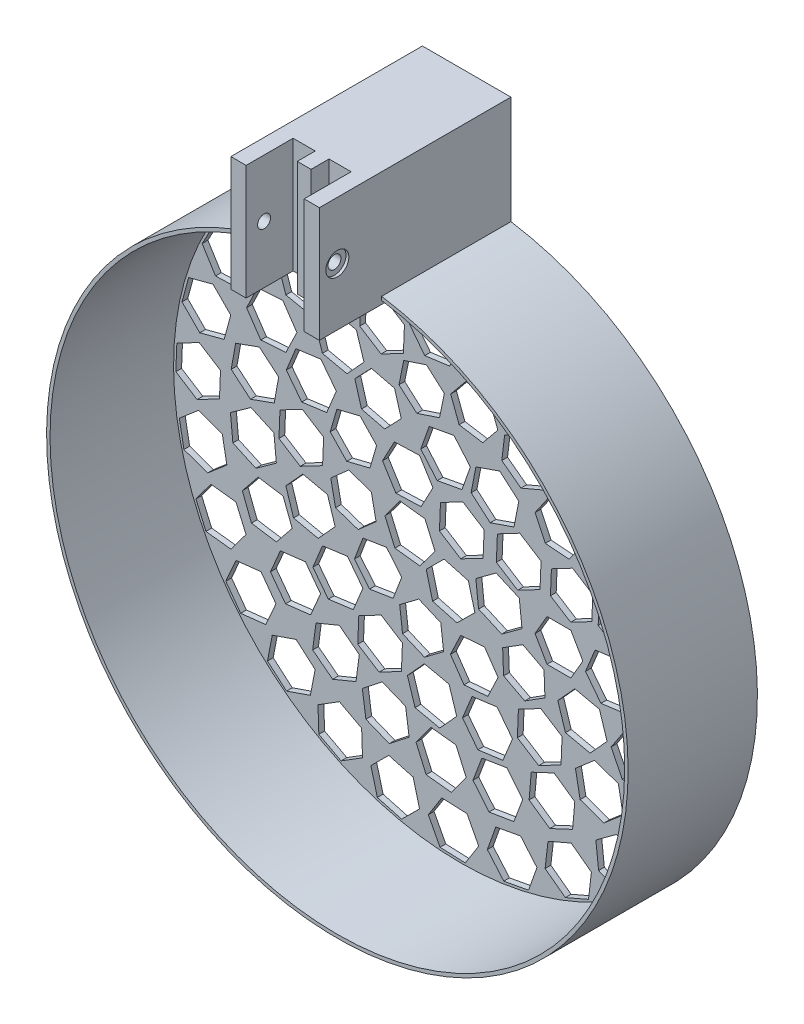
SolidWorks part; units mm, degrees
ref_plane "Plan de face" through (0, 0, 0) normal (0, 0, 1) x (1, 0, 0)
ref_plane "Plan de dessus" through (0, 0, 0) normal (0, 1, 0) x (1, 0, 0)
ref_plane "Plan de droite" through (0, 0, 0) normal (1, 0, 0) x (0, 0, -1)
sketch "Base" plane through (0, 0, 0) normal (0, 1, 0) x (1, 0, 0)
  line L0 (-3.85, -2.4) -> (-3.85, 2.4)
  line L1 (-3.85, 2.4) -> (-10.1, 2.4)
  line L2 (-10.1, 2.4) -> (-10.1, 10.1)
  line L3 (-10.1, 10.1) -> (-2.4, 10.1)
  line L4 (-2.4, 10.1) -> (-2.4, 3.85)
  line L5 (-2.4, 3.85) -> (2.4, 3.85)
  line L6 (0, -55) -> (0, 55) construction
  line L7 (2.4, 10.1) -> (2.4, 3.85)
  line L8 (10.1, 10.1) -> (2.4, 10.1)
  line L9 (10.1, 2.4) -> (10.1, 10.1)
  line L10 (3.85, 2.4) -> (10.1, 2.4)
  line L11 (3.85, -2.4) -> (3.85, 2.4)
  line L12 (-55, 0) -> (55, 0) construction
  line L13 (3.85, -2.4) -> (10.1, -2.4)
  line L14 (10.1, -2.4) -> (10.1, -6.25)
  line L20 (-10.1, -2.4) -> (-10.1, -6.25)
  line L21 (-3.85, -2.4) -> (-10.1, -2.4)
  line L23 (-15.4, 15.4) -> (15.4, 15.4)
  line L24 (-15.4, 15.4) -> (-15.4, -6.25)
  line L26 (15.4, 15.4) -> (15.4, -6.25)
  line L27 (-15.4, 15.4) -> (0, 0) construction
  line L28 (0, 0) -> (15.4, 15.4) construction
  line L29 (-10.1, -6.25) -> (-15.4, -6.25)
  line L30 (10.1, -6.25) -> (15.4, -6.25)
  line L31 (10.1, -10.1) -> (15.4, -15.4) construction
  point P2 (-3.85, 0)
  point P3 (0, 3.85)
  point P27 (0, 0)
  dimension "D1" = 4.8
  dimension "D2" = 4.8
  dimension "D3" = 6.25
  dimension "D4" = 7.7
  dimension "D5" = 30.8
extrude "Boss.-Extru.1" add sketch "Base" along normal mid plane 40
hole_wizard "Chambrage pour vis à six pans creux M41" positions "Esquisse4" profile "Esquisse5" counterbore size "M4" standard "ISO" end condition up to next
sketch "Esquisse4" plane through (15.4, 0, 0) normal (1, 0, 0) x (0, 0, -1)
  point P0 (0, 0)
sketch "Esquisse5" plane through (15.4, 0, 0) normal (0, 1, 0) x (0, 0, -1)
  line L0 (0, 0) -> (0, 11.55)
  line L1 (0, 11.55) -> (2.25, 11.55)
  line L3 (2.25, 11.55) -> (2.25, 1)
  line L4 (2.25, 1) -> (4, 1)
  line L5 (4, 1) -> (4, 0)
  line L7 (4, 0) -> (0, 0)
  line L11 (0, -6.35) -> (0, 107.95) construction
  dimension "Diamètre du perçage jusqu'au prochain" = 4.5
  dimension "Profondeur du perçage jusqu'au prochain" = 11.55
  dimension "Diamètre du chambrage" = 8
  dimension "Profondeur du chambrage" = 1
mirror "Symétrie1" about plane through (0, 0, 0) normal (1, 0, 0) of "Chambrage pour vis à six pans creux M41"
sketch "Esquisse6" plane through (0, 0, 0) normal (0, 0, 1) x (1, 0, 0)
  line L0 (10.1, 20) -> (10.1, -20) construction
  line L1 (-10.1, 20) -> (10.1, 20)
  line L2 (-10.1, 20) -> (-10.1, -20)
  line L3 (-10.1, -20) -> (10.1, -20)
  line L4 (10.1, 20) -> (10.1, -20)
  line L5 (-10.1, 20) -> (10.1, -20) construction
  line L6 (-10.1, -20) -> (10.1, 20) construction
  line L7 (-10.1, 20) -> (-3.85, 20) construction
  point P0 (0, 0)
extrude "Enlèv. mat.-Extru.1" cut sketch "Esquisse6" against normal mid plane 6
sketch "Esquisse16" plane through (0, 0, -15.4) normal (0, 0, -1) x (-1, 0, 0)
  circle A0 centre (0, -117.5665) radius 100
extrude "Extru.-Mince1" add sketch "Esquisse16" along normal blind 45 thin thin type one direction wall 1.2
sketch "Esquisse14" plane through (0, -20, 0) normal (0, -1, 0) x (1, 0, 0)
  line L0 (15.4, 6.25) -> (15.4, -15.4) construction
  line L1 (-15.4, -15.4) -> (15.4, -15.4)
  line L2 (-15.4, -15.4) -> (-15.4, -60.4)
  line L3 (-15.4, -60.4) -> (15.4, -60.4)
  line L4 (15.4, -15.4) -> (15.4, -60.4)
  dimension "D1" = 45
extrude "Boss.-Extru.3" add sketch "Esquisse14" against normal up to vertex (40 mm away) up to point (-15.4, 20, -15.4)
ref_plane "Plan1" through (15.4, -18.7594, -60.4) normal (0.9881, -0.154, 0) x (0, 0, -1)
sketch "Esquisse17" plane through (0, 0, -60.4) normal (0, 0, -1) x (-1, 0, 0)
  circle A0 centre (0, -117.5665) radius 100
extrude "Boss.-Extru.4" add sketch "Esquisse17" against normal blind 2
sketch "Esquisse18" plane through (0, 0, -60.4) normal (0, 0, -1) x (-1, 0, 0)
  line L0 (-29.3876, -106.503) -> (-25.8265, -98.9869)
  line L1 (-31.1629, -121.4274) -> (-31.5026, -113.1172)
  line L2 (-31.5026, -113.1172) -> (-38.8692, -109.2564)
  line L3 (-38.8692, -109.2564) -> (-45.8961, -113.7056)
  line L4 (-45.8961, -113.7056) -> (-45.5564, -122.0158)
  line L5 (-45.5564, -122.0158) -> (-38.1898, -125.8766)
  line L6 (-38.1898, -125.8766) -> (-31.1629, -121.4274)
  line L7 (-25.8265, -98.9869) -> (-30.5551, -92.1448)
  line L8 (-30.5551, -92.1448) -> (-38.8448, -92.8189)
  line L9 (-38.8448, -92.8189) -> (-42.4059, -100.335)
  line L10 (-42.4059, -100.335) -> (-37.6773, -107.177)
  line L11 (-37.6773, -107.177) -> (-29.3876, -106.503)
  line L12 (-20.88, -94.1131) -> (-14.2339, -89.1129)
  line L13 (-14.2339, -89.1129) -> (-15.2412, -80.8571)
  line L14 (-15.2412, -80.8571) -> (-22.8946, -77.6015)
  line L15 (-22.8946, -77.6015) -> (-29.5407, -82.6018)
  line L16 (-29.5407, -82.6018) -> (-28.5334, -90.8576)
  line L17 (-28.5334, -90.8576) -> (-20.88, -94.1131)
  line L18 (-7.589, -87.0962) -> (0.6196, -85.7573)
  line L19 (0.6196, -85.7573) -> (3.5643, -77.979)
  line L20 (3.5643, -77.979) -> (-1.6995, -71.5396)
  line L21 (-1.6995, -71.5396) -> (-9.908, -72.8785)
  line L22 (-9.908, -72.8785) -> (-12.8528, -80.6568)
  line L23 (-12.8528, -80.6568) -> (-7.589, -87.0962)
  line L24 (7.4406, -87.0596) -> (15.3311, -89.6888)
  line L25 (15.3311, -89.6888) -> (21.5533, -84.1699)
  line L26 (21.5533, -84.1699) -> (19.885, -76.0219)
  line L27 (19.885, -76.0219) -> (11.9944, -73.3928)
  line L28 (11.9944, -73.3928) -> (5.7722, -78.9116)
  line L29 (5.7722, -78.9116) -> (7.4406, -87.0596)
  line L30 (20.7656, -94.0118) -> (26.5304, -100.0067)
  line L31 (26.5304, -100.0067) -> (34.6047, -98.0116)
  line L32 (34.6047, -98.0116) -> (36.914, -90.0216)
  line L33 (36.914, -90.0216) -> (31.1491, -84.0267)
  line L34 (31.1491, -84.0267) -> (23.0749, -86.0218)
  line L35 (23.0749, -86.0218) -> (20.7656, -94.0118)
  line L36 (29.3334, -106.3601) -> (31.652, -114.3474)
  line L37 (31.652, -114.3474) -> (39.7285, -116.3331)
  line L38 (39.7285, -116.3331) -> (45.4864, -110.3315)
  line L39 (45.4864, -110.3315) -> (43.1679, -102.3442)
  line L40 (43.1679, -102.3442) -> (35.0913, -100.3585)
  line L41 (35.0913, -100.3585) -> (29.3334, -106.3601)
  line L42 (31.1813, -121.2756) -> (29.5224, -129.4255)
  line L43 (29.5224, -129.4255) -> (35.751, -134.9371)
  line L44 (35.751, -134.9371) -> (43.6385, -132.2988)
  line L45 (43.6385, -132.2988) -> (45.2974, -124.1489)
  line L46 (45.2974, -124.1489) -> (39.0688, -118.6373)
  line L47 (39.0688, -118.6373) -> (31.1813, -121.2756)
  line L48 (25.886, -135.3414) -> (20.6296, -141.7869)
  line L49 (20.6296, -141.7869) -> (23.5834, -149.5618)
  line L50 (23.5834, -149.5618) -> (31.7935, -150.8912)
  line L51 (31.7935, -150.8912) -> (37.0499, -144.4457)
  line L52 (37.0499, -144.4457) -> (34.0961, -136.6708)
  line L53 (34.0961, -136.6708) -> (25.886, -135.3414)
  line L54 (14.6605, -145.3352) -> (7.0109, -148.5997)
  line L55 (7.0109, -148.5997) -> (6.0131, -156.8567)
  line L56 (6.0131, -156.8567) -> (12.665, -161.8492)
  line L57 (12.665, -161.8492) -> (20.3147, -158.5848)
  line L58 (20.3147, -158.5848) -> (21.3124, -150.3278)
  line L59 (21.3124, -150.3278) -> (14.6605, -145.3352)
  line L60 (0.0764, -148.9676) -> (-8.214, -148.3031)
  line L61 (-8.214, -148.3031) -> (-12.9347, -155.1507)
  line L62 (-12.9347, -155.1507) -> (-9.3649, -162.6626)
  line L63 (-9.3649, -162.6626) -> (-1.0744, -163.3271)
  line L64 (-1.0744, -163.3271) -> (3.6462, -156.4795)
  line L65 (3.6462, -156.4795) -> (0.0764, -148.9676)
  line L66 (-14.5251, -145.4063) -> (-21.5572, -140.9652)
  line L67 (-21.5572, -140.9652) -> (-28.9193, -144.8346)
  line L68 (-28.9193, -144.8346) -> (-29.2494, -153.1451)
  line L69 (-29.2494, -153.1451) -> (-22.2173, -157.5862)
  line L70 (-22.2173, -157.5862) -> (-14.8552, -153.7168)
  line L71 (-14.8552, -153.7168) -> (-14.5251, -145.4063)
  line L72 (-25.7992, -135.4672) -> (-29.9619, -128.2669)
  line L73 (-29.9619, -128.2669) -> (-38.2789, -128.2717)
  line L74 (-38.2789, -128.2717) -> (-42.4332, -135.4769)
  line L75 (-42.4332, -135.4769) -> (-38.2705, -142.6772)
  line L76 (-38.2705, -142.6772) -> (-29.9535, -142.6724)
  line L77 (-29.9535, -142.6724) -> (-25.7992, -135.4672)
  line L78 (-47.7791, -122.0417) -> (-48.1377, -113.2706)
  line L79 (-48.1377, -113.2706) -> (-55.913, -109.1955)
  line L80 (-55.913, -109.1955) -> (-63.3297, -113.8916)
  line L81 (-63.3297, -113.8916) -> (-62.9711, -122.6627)
  line L82 (-62.9711, -122.6627) -> (-55.1958, -126.7378)
  line L83 (-55.1958, -126.7378) -> (-47.7791, -122.0417)
  line L84 (-46.4283, -105.4304) -> (-43.7653, -97.0656)
  line L85 (-43.7653, -97.0656) -> (-49.6779, -90.577)
  line L86 (-49.6779, -90.577) -> (-58.2536, -92.4532)
  line L87 (-58.2536, -92.4532) -> (-60.9165, -100.818)
  line L88 (-60.9165, -100.818) -> (-55.0039, -107.3066)
  line L89 (-55.0039, -107.3066) -> (-46.4283, -105.4304)
  line L90 (-39.4775, -90.2829) -> (-34.1142, -83.3333)
  line L91 (-34.1142, -83.3333) -> (-37.451, -75.2138)
  line L92 (-37.451, -75.2138) -> (-46.1512, -74.0438)
  line L93 (-46.1512, -74.0438) -> (-51.5145, -80.9934)
  line L94 (-51.5145, -80.9934) -> (-48.1777, -89.1129)
  line L95 (-48.1777, -89.1129) -> (-39.4775, -90.2829)
  line L96 (-27.7652, -78.4262) -> (-20.3484, -73.7301)
  line L97 (-20.3484, -73.7301) -> (-20.707, -64.959)
  line L98 (-20.707, -64.959) -> (-28.4823, -60.8839)
  line L99 (-28.4823, -60.8839) -> (-35.899, -65.58)
  line L100 (-35.899, -65.58) -> (-35.5405, -74.3511)
  line L101 (-35.5405, -74.3511) -> (-27.7652, -78.4262)
  line L102 (-12.704, -71.2904) -> (-4.1283, -69.4142)
  line L103 (-4.1283, -69.4142) -> (-1.4654, -61.0494)
  line L104 (-1.4654, -61.0494) -> (-7.378, -54.5608)
  line L105 (-7.378, -54.5608) -> (-15.9536, -56.437)
  line L106 (-15.9536, -56.437) -> (-18.6166, -64.8018)
  line L107 (-18.6166, -64.8018) -> (-12.704, -71.2904)
  line L108 (3.8895, -69.7362) -> (12.5897, -70.9061)
  line L109 (12.5897, -70.9061) -> (17.953, -63.9566)
  line L110 (17.953, -63.9566) -> (14.6162, -55.8371)
  line L111 (14.6162, -55.8371) -> (5.916, -54.6671)
  line L112 (5.916, -54.6671) -> (0.5527, -61.6166)
  line L113 (0.5527, -61.6166) -> (3.8895, -69.7362)
  line L114 (20.0139, -73.951) -> (27.7892, -78.026)
  line L115 (27.7892, -78.026) -> (35.206, -73.3299)
  line L116 (35.206, -73.3299) -> (34.8474, -64.5588)
  line L117 (34.8474, -64.5588) -> (27.0721, -60.4838)
  line L118 (27.0721, -60.4838) -> (19.6554, -65.1799)
  line L119 (19.6554, -65.1799) -> (20.0139, -73.951)
  line L120 (33.7243, -83.4265) -> (39.637, -89.9151)
  line L121 (39.637, -89.9151) -> (48.2126, -88.0389)
  line L122 (48.2126, -88.0389) -> (50.8755, -79.6741)
  line L123 (50.8755, -79.6741) -> (44.9629, -73.1855)
  line L124 (44.9629, -73.1855) -> (36.3873, -75.0617)
  line L125 (36.3873, -75.0617) -> (33.7243, -83.4265)
  line L126 (43.3671, -97.0198) -> (46.7039, -105.1393)
  line L127 (46.7039, -105.1393) -> (55.404, -106.3093)
  line L128 (55.404, -106.3093) -> (60.7673, -99.3597)
  line L129 (60.7673, -99.3597) -> (57.4305, -91.2402)
  line L130 (57.4305, -91.2402) -> (48.7304, -90.0702)
  line L131 (48.7304, -90.0702) -> (43.3671, -97.0198)
  line L132 (47.7791, -113.0913) -> (48.1377, -121.8624)
  line L133 (48.1377, -121.8624) -> (55.913, -125.9375)
  line L134 (55.913, -125.9375) -> (63.3297, -121.2414)
  line L135 (63.3297, -121.2414) -> (62.9711, -112.4703)
  line L136 (62.9711, -112.4703) -> (55.1958, -108.3952)
  line L137 (55.1958, -108.3952) -> (47.7791, -113.0913)
  line L138 (46.4283, -129.7026) -> (43.7653, -138.0674)
  line L139 (43.7653, -138.0674) -> (49.6779, -144.556)
  line L140 (49.6779, -144.556) -> (58.2536, -142.6798)
  line L141 (58.2536, -142.6798) -> (60.9165, -134.315)
  line L142 (60.9165, -134.315) -> (55.0039, -127.8264)
  line L143 (55.0039, -127.8264) -> (46.4283, -129.7026)
  line L144 (39.4775, -144.8501) -> (34.1142, -151.7997)
  line L145 (34.1142, -151.7997) -> (37.451, -159.9192)
  line L146 (37.451, -159.9192) -> (46.1512, -161.0892)
  line L147 (46.1512, -161.0892) -> (51.5145, -154.1396)
  line L148 (51.5145, -154.1396) -> (48.1777, -146.0201)
  line L149 (48.1777, -146.0201) -> (39.4775, -144.8501)
  line L150 (27.7652, -156.7068) -> (20.3484, -161.4029)
  line L151 (20.3484, -161.4029) -> (20.707, -170.174)
  line L152 (20.707, -170.174) -> (28.4823, -174.2491)
  line L153 (28.4823, -174.2491) -> (35.899, -169.553)
  line L154 (35.899, -169.553) -> (35.5405, -160.7819)
  line L155 (35.5405, -160.7819) -> (27.7652, -156.7068)
  line L156 (12.704, -163.8426) -> (4.1283, -165.7188)
  line L157 (4.1283, -165.7188) -> (1.4654, -174.0836)
  line L158 (1.4654, -174.0836) -> (7.378, -180.5722)
  line L159 (7.378, -180.5722) -> (15.9536, -178.696)
  line L160 (15.9536, -178.696) -> (18.6166, -170.3312)
  line L161 (18.6166, -170.3312) -> (12.704, -163.8426)
  line L162 (-3.8895, -165.3968) -> (-12.5897, -164.2269)
  line L163 (-12.5897, -164.2269) -> (-17.953, -171.1764)
  line L164 (-17.953, -171.1764) -> (-14.6162, -179.2959)
  line L165 (-14.6162, -179.2959) -> (-5.916, -180.4659)
  line L166 (-5.916, -180.4659) -> (-0.5527, -173.5164)
  line L167 (-0.5527, -173.5164) -> (-3.8895, -165.3968)
  line L168 (-20.0139, -161.182) -> (-27.7892, -157.107)
  line L169 (-27.7892, -157.107) -> (-35.206, -161.8031)
  line L170 (-35.206, -161.8031) -> (-34.8474, -170.5742)
  line L171 (-34.8474, -170.5742) -> (-27.0721, -174.6492)
  line L172 (-27.0721, -174.6492) -> (-19.6554, -169.9531)
  line L173 (-19.6554, -169.9531) -> (-20.0139, -161.182)
  line L174 (-33.7243, -151.7065) -> (-39.637, -145.2179)
  line L175 (-39.637, -145.2179) -> (-48.2126, -147.0941)
  line L176 (-48.2126, -147.0941) -> (-50.8755, -155.4589)
  line L177 (-50.8755, -155.4589) -> (-44.9629, -161.9475)
  line L178 (-44.9629, -161.9475) -> (-36.3873, -160.0713)
  line L179 (-36.3873, -160.0713) -> (-33.7243, -151.7065)
  line L180 (-43.3671, -138.1132) -> (-46.7039, -129.9937)
  line L181 (-46.7039, -129.9937) -> (-55.404, -128.8237)
  line L182 (-55.404, -128.8237) -> (-60.7673, -135.7733)
  line L183 (-60.7673, -135.7733) -> (-57.4305, -143.8928)
  line L184 (-57.4305, -143.8928) -> (-48.7304, -145.0628)
  line L185 (-48.7304, -145.0628) -> (-43.3671, -138.1132)
  line L186 (-64.853, -123.5923) -> (-65.2116, -114.8211)
  line L187 (-65.2116, -114.8211) -> (-72.9869, -110.7461)
  line L188 (-72.9869, -110.7461) -> (-80.4036, -115.4422)
  line L189 (-80.4036, -115.4422) -> (-80.045, -124.2133)
  line L190 (-80.045, -124.2133) -> (-72.2697, -128.2884)
  line L191 (-72.2697, -128.2884) -> (-64.853, -123.5923)
  line L192 (-64.0738, -105.8717) -> (-62.0526, -97.3291)
  line L193 (-62.0526, -97.3291) -> (-68.4402, -91.3074)
  line L194 (-68.4402, -91.3074) -> (-76.8489, -93.8283)
  line L195 (-76.8489, -93.8283) -> (-78.87, -102.3709)
  line L196 (-72.4825, -108.3926) -> (-64.0738, -105.8717)
  line L197 (-78.87, -102.3709) -> (-72.4825, -108.3926)
  line L198 (-58.5426, -89.0185) -> (-54.2916, -81.3379)
  line L199 (-54.2916, -81.3379) -> (-58.8176, -73.8162)
  line L200 (-58.8176, -73.8162) -> (-67.5946, -73.975)
  line L201 (-67.5946, -73.975) -> (-71.8456, -81.6555)
  line L202 (-67.3196, -89.1773) -> (-58.5426, -89.0185)
  line L203 (-71.8456, -81.6555) -> (-67.3196, -89.1773)
  line L204 (-48.6695, -74.2825) -> (-42.5039, -68.0337)
  line L205 (-42.5039, -68.0337) -> (-44.8328, -59.5698)
  line L206 (-44.8328, -59.5698) -> (-53.3272, -57.3547)
  line L207 (-53.3272, -57.3547) -> (-59.4927, -63.6035)
  line L208 (-57.1639, -72.0674) -> (-48.6695, -74.2825)
  line L209 (-59.4927, -63.6035) -> (-57.1639, -72.0674)
  line L210 (-35.1868, -62.7567) -> (-27.564, -58.4031)
  line L211 (-27.564, -58.4031) -> (-27.523, -49.6247)
  line L212 (-27.523, -49.6247) -> (-35.1047, -45.2)
  line L213 (-35.1047, -45.2) -> (-42.7275, -49.5536)
  line L214 (-42.7686, -58.332) -> (-35.1868, -62.7567)
  line L215 (-42.7275, -49.5536) -> (-42.7686, -58.332)
  line L216 (-19.0945, -55.2959) -> (-10.5797, -53.1603)
  line L217 (-10.5797, -53.1603) -> (-8.1719, -44.7186)
  line L218 (-8.1719, -44.7186) -> (-14.2787, -38.4124)
  line L219 (-14.2787, -38.4124) -> (-22.7934, -40.548)
  line L220 (-25.2013, -48.9898) -> (-19.0945, -55.2959)
  line L221 (-22.7934, -40.548) -> (-25.2013, -48.9898)
  line L222 (-1.586, -52.4535) -> (7.1892, -52.6943)
  line L223 (7.1892, -52.6943) -> (11.7853, -45.2152)
  line L224 (11.7853, -45.2152) -> (7.6063, -37.4953)
  line L225 (7.6063, -37.4953) -> (-1.1688, -37.2545)
  line L226 (-5.765, -44.7335) -> (-1.586, -52.4535)
  line L227 (-1.1688, -37.2545) -> (-5.765, -44.7335)
  line L228 (16.0401, -54.4401) -> (24.4249, -57.0396)
  line L229 (24.4249, -57.0396) -> (30.8684, -51.0778)
  line L230 (30.8684, -51.0778) -> (28.9272, -42.5167)
  line L231 (28.9272, -42.5167) -> (20.5424, -39.9173)
  line L232 (14.0989, -45.879) -> (16.0401, -54.4401)
  line L233 (20.5424, -39.9173) -> (14.0989, -45.879)
  line L234 (32.4766, -61.1086) -> (39.8491, -65.8738)
  line L235 (39.8491, -65.8738) -> (47.6622, -61.8716)
  line L236 (47.6622, -61.8716) -> (48.1027, -53.1042)
  line L237 (48.1027, -53.1042) -> (40.7302, -48.339)
  line L238 (32.9171, -52.3412) -> (32.4766, -61.1086)
  line L239 (40.7302, -48.339) -> (32.9171, -52.3412)
  line L240 (46.5044, -71.9643) -> (52.3179, -78.5419)
  line L241 (52.3179, -78.5419) -> (60.921, -76.796)
  line L242 (60.921, -76.796) -> (63.7106, -68.4726)
  line L243 (63.7106, -68.4726) -> (57.8971, -61.895)
  line L244 (49.294, -63.6409) -> (46.5044, -71.9643)
  line L245 (57.8971, -61.895) -> (49.294, -63.6409)
  line L246 (57.0832, -86.2021) -> (60.9065, -94.1042)
  line L247 (60.9065, -94.1042) -> (69.6616, -94.7442)
  line L248 (69.6616, -94.7442) -> (74.5934, -87.4821)
  line L249 (74.5934, -87.4821) -> (70.7701, -79.5799)
  line L250 (62.015, -78.94) -> (57.0832, -86.2021)
  line L251 (70.7701, -79.5799) -> (62.015, -78.94)
  line L252 (63.4284, -102.766) -> (64.978, -111.4067)
  line L253 (64.978, -111.4067) -> (73.2358, -114.385)
  line L254 (73.2358, -114.385) -> (79.944, -108.7228)
  line L255 (79.944, -108.7228) -> (78.3944, -100.0821)
  line L256 (70.1367, -97.1038) -> (63.4284, -102.766)
  line L257 (78.3944, -100.0821) -> (70.1367, -97.1038)
  line L258 (65.0695, -120.4277) -> (64.2303, -129.1659)
  line L259 (64.2303, -129.1659) -> (71.3783, -134.2618)
  line L260 (71.3783, -134.2618) -> (79.3655, -130.6193)
  line L261 (79.3655, -130.6193) -> (80.2046, -121.8811)
  line L262 (73.0566, -116.7852) -> (65.0695, -120.4277)
  line L263 (80.2046, -121.8811) -> (73.0566, -116.7852)
  line L264 (61.8846, -137.8771) -> (58.719, -146.0649)
  line L265 (58.719, -146.0649) -> (64.2271, -152.9003)
  line L266 (64.2271, -152.9003) -> (72.9008, -151.5478)
  line L267 (72.9008, -151.5478) -> (76.0663, -143.36)
  line L268 (70.5582, -136.5246) -> (61.8846, -137.8771)
  line L269 (76.0663, -143.36) -> (70.5582, -136.5246)
  line L270 (54.11, -153.8202) -> (48.8528, -160.8503)
  line L271 (48.8528, -160.8503) -> (52.3125, -168.9183)
  line L272 (52.3125, -168.9183) -> (61.0293, -169.9561)
  line L273 (61.0293, -169.9561) -> (66.2866, -162.926)
  line L274 (62.8269, -154.858) -> (54.11, -153.8202)
  line L275 (66.2866, -162.926) -> (62.8269, -154.858)
  line L276 (42.3223, -167.0745) -> (35.3633, -172.4256)
  line L277 (35.3633, -172.4256) -> (36.518, -181.1278)
  line L278 (36.518, -181.1278) -> (44.6317, -184.4789)
  line L279 (44.6317, -184.4789) -> (51.5906, -179.1278)
  line L280 (50.436, -170.4256) -> (42.3223, -167.0745)
  line L281 (51.5906, -179.1278) -> (50.436, -170.4256)
  line L282 (27.3958, -176.657) -> (19.2512, -179.9322)
  line L283 (19.2512, -179.9322) -> (18.0152, -188.6232)
  line L284 (18.0152, -188.6232) -> (24.9239, -194.0391)
  line L285 (24.9239, -194.0391) -> (33.0685, -190.7639)
  line L286 (34.3044, -182.0729) -> (27.3958, -176.657)
  line L287 (33.0685, -190.7639) -> (34.3044, -182.0729)
  line L288 (10.4374, -181.8571) -> (1.7112, -182.8134)
  line L289 (1.7112, -182.8134) -> (-1.8237, -190.8487)
  line L290 (-1.8237, -190.8487) -> (3.3676, -197.9276)
  line L291 (3.3676, -197.9276) -> (12.0938, -196.9714)
  line L292 (15.6287, -188.9361) -> (10.4374, -181.8571)
  line L293 (12.0938, -196.9714) -> (15.6287, -188.9361)
  line L294 (-7.295, -182.289) -> (-15.9556, -180.8555)
  line L295 (-15.9556, -180.8555) -> (-21.5274, -187.6391)
  line L296 (-21.5274, -187.6391) -> (-18.4385, -195.8562)
  line L297 (-18.4385, -195.8562) -> (-9.7779, -197.2897)
  line L298 (-4.2061, -190.5061) -> (-7.295, -182.289)
  line L299 (-9.7779, -197.2897) -> (-4.2061, -190.5061)
  line L300 (-24.4864, -177.9208) -> (-32.4391, -174.2038)
  line L301 (-32.4391, -174.2038) -> (-39.6344, -179.2326)
  line L302 (-39.6344, -179.2326) -> (-38.877, -187.9783)
  line L303 (-38.877, -187.9783) -> (-30.9243, -191.6953)
  line L304 (-23.729, -186.6665) -> (-24.4864, -177.9208)
  line L305 (-30.9243, -191.6953) -> (-23.729, -186.6665)
  line L306 (-39.8618, -169.0763) -> (-46.5168, -163.3516)
  line L307 (-46.5168, -163.3516) -> (-54.802, -166.2526)
  line L308 (-54.802, -166.2526) -> (-56.4323, -174.8784)
  line L309 (-56.4323, -174.8784) -> (-49.7773, -180.6031)
  line L310 (-41.492, -177.7021) -> (-39.8618, -169.0763)
  line L311 (-49.7773, -180.6031) -> (-41.492, -177.7021)
  line L312 (-52.2808, -156.4116) -> (-57.1445, -149.1037)
  line L313 (-57.1445, -149.1037) -> (-65.9052, -149.6618)
  line L314 (-65.9052, -149.6618) -> (-69.8022, -157.5279)
  line L315 (-69.8022, -157.5279) -> (-64.9385, -164.8358)
  line L316 (-56.1778, -164.2777) -> (-52.2808, -156.4116)
  line L317 (-64.9385, -164.8358) -> (-56.1778, -164.2777)
  line L318 (-60.8223, -140.8659) -> (-63.534, -132.5168)
  line L319 (-63.534, -132.5168) -> (-72.1204, -130.6906)
  line L320 (-72.1204, -130.6906) -> (-77.9952, -137.2136)
  line L321 (-77.9952, -137.2136) -> (-75.2835, -145.5627)
  line L322 (-66.6971, -147.3889) -> (-60.8223, -140.8659)
  line L323 (-75.2835, -145.5627) -> (-66.6971, -147.3889)
  line L324 (-12.3377, -120.7572) -> (-12.6963, -111.9861)
  line L325 (-12.6963, -111.9861) -> (-20.4716, -107.911)
  line L326 (-20.4716, -107.911) -> (-27.8883, -112.6071)
  line L327 (-27.8883, -112.6071) -> (-27.5298, -121.3783)
  line L328 (-27.5298, -121.3783) -> (-19.7545, -125.4533)
  line L329 (-19.7545, -125.4533) -> (-12.3377, -120.7572)
  line L330 (-10.1871, -109.9098) -> (-3.5531, -104.1608)
  line L331 (-3.5531, -104.1608) -> (-5.2149, -95.5411)
  line L332 (-5.2149, -95.5411) -> (-13.5107, -92.6704)
  line L333 (-20.1447, -98.4194) -> (-18.4829, -107.0392)
  line L334 (-18.4829, -107.0392) -> (-10.1871, -109.9098)
  line L335 (-13.5107, -92.6704) -> (-20.1447, -98.4194)
  line L336 (-0.3653, -104.8281) -> (8.2657, -106.4303)
  line L337 (8.2657, -106.4303) -> (13.9687, -99.7567)
  line L338 (13.9687, -99.7567) -> (11.0408, -91.4809)
  line L339 (2.4098, -89.8788) -> (-3.2933, -96.5523)
  line L340 (-3.2933, -96.5523) -> (-0.3653, -104.8281)
  line L341 (11.0408, -91.4809) -> (2.4098, -89.8788)
  line L342 (9.7315, -109.3386) -> (13.8602, -117.0856)
  line L343 (13.8602, -117.0856) -> (22.6336, -117.3835)
  line L344 (22.6336, -117.3835) -> (27.2783, -109.9344)
  line L345 (23.1496, -102.1875) -> (14.3762, -101.8896)
  line L346 (14.3762, -101.8896) -> (9.7315, -109.3386)
  line L347 (27.2783, -109.9344) -> (23.1496, -102.1875)
  line L348 (12.5003, -120.0449) -> (9.0177, -128.103)
  line L349 (9.0177, -128.103) -> (14.2549, -135.1481)
  line L350 (14.2549, -135.1481) -> (22.9747, -134.135)
  line L351 (26.4573, -126.077) -> (21.2201, -119.0319)
  line L352 (21.2201, -119.0319) -> (12.5003, -120.0449)
  line L353 (22.9747, -134.135) -> (26.4573, -126.077)
  line L354 (5.8561, -128.8849) -> (-2.6153, -131.1862)
  line L355 (-2.6153, -131.1862) -> (-4.858, -139.6734)
  line L356 (-4.858, -139.6734) -> (1.3707, -145.8592)
  line L357 (9.8421, -143.5579) -> (12.0848, -135.0707)
  line L358 (12.0848, -135.0707) -> (5.8561, -128.8849)
  line L359 (1.3707, -145.8592) -> (9.8421, -143.5579)
  line L360 (-5.1979, -129.2019) -> (-12.279, -124.0135)
  line L361 (-12.279, -124.0135) -> (-20.3128, -127.5518)
  line L362 (-20.3128, -127.5518) -> (-21.2655, -136.2784)
  line L363 (-14.1844, -141.4667) -> (-6.1506, -137.9285)
  line L364 (-6.1506, -137.9285) -> (-5.1979, -129.2019)
  line L365 (-21.2655, -136.2784) -> (-14.1844, -141.4667)
  line L366 (-83.6712, -124.2141) -> (-84.0298, -115.443)
  line L367 (-84.0298, -115.443) -> (-91.8051, -111.3679)
  line L368 (-91.8051, -111.3679) -> (-99.2218, -116.064)
  line L369 (-99.2218, -116.064) -> (-98.8633, -124.8351)
  line L370 (-98.8633, -124.8351) -> (-91.088, -128.9102)
  line L371 (-91.088, -128.9102) -> (-83.6712, -124.2141)
  line L372 (7.4712, -121.2135) -> (7.1126, -112.4423)
  line L373 (7.1126, -112.4423) -> (-0.6627, -108.3673)
  line L374 (-0.6627, -108.3673) -> (-8.0794, -113.0634)
  line L375 (-8.0794, -113.0634) -> (-7.7209, -121.8345)
  line L376 (-7.7209, -121.8345) -> (0.0544, -125.9096)
  line L377 (0.0544, -125.9096) -> (7.4712, -121.2135)
  line L378 (-83.0526, -105.4288) -> (-81.4504, -96.7978)
  line L379 (-81.4504, -96.7978) -> (-88.124, -91.0948)
  line L380 (-88.124, -91.0948) -> (-96.3998, -94.0227)
  line L381 (-96.3998, -94.0227) -> (-98.002, -102.6537)
  line L382 (-98.002, -102.6537) -> (-91.3284, -108.3568)
  line L383 (-91.3284, -108.3568) -> (-83.0526, -105.4288)
  line L384 (-78.2694, -87.2522) -> (-74.7868, -79.1941)
  line L385 (-74.7868, -79.1941) -> (-80.024, -72.149)
  line L386 (-80.024, -72.149) -> (-88.7439, -73.1621)
  line L387 (-88.7439, -73.1621) -> (-92.2265, -81.2202)
  line L388 (-92.2265, -81.2202) -> (-86.9893, -88.2652)
  line L389 (-86.9893, -88.2652) -> (-78.2694, -87.2522)
  line L390 (-69.5615, -70.5956) -> (-64.3731, -63.5145)
  line L391 (-64.3731, -63.5145) -> (-67.9113, -55.4807)
  line L392 (-67.9113, -55.4807) -> (-76.6379, -54.528)
  line L393 (-76.6379, -54.528) -> (-81.8263, -61.6091)
  line L394 (-81.8263, -61.6091) -> (-78.2881, -69.6429)
  line L395 (-78.2881, -69.6429) -> (-69.5615, -70.5956)
  line L396 (-57.3654, -56.2944) -> (-50.7315, -50.5454)
  line L397 (-50.7315, -50.5454) -> (-52.3933, -41.9256)
  line L398 (-52.3933, -41.9256) -> (-60.6891, -39.055)
  line L399 (-60.6891, -39.055) -> (-67.3231, -44.804)
  line L400 (-67.3231, -44.804) -> (-65.6613, -53.4237)
  line L401 (-65.6613, -53.4237) -> (-57.3654, -56.2944)
  line L402 (-42.2929, -45.0656) -> (-34.5459, -40.9369)
  line L403 (-34.5459, -40.9369) -> (-34.248, -32.1635)
  line L404 (-34.248, -32.1635) -> (-41.697, -27.5188)
  line L405 (-41.697, -27.5188) -> (-49.444, -31.6475)
  line L406 (-49.444, -31.6475) -> (-49.7419, -40.4209)
  line L407 (-49.7419, -40.4209) -> (-42.2929, -45.0656)
  line L408 (-25.0995, -37.4723) -> (-16.6281, -35.171)
  line L409 (-16.6281, -35.171) -> (-14.3854, -26.6839)
  line L410 (-14.3854, -26.6839) -> (-20.6141, -20.498)
  line L411 (-20.6141, -20.498) -> (-29.0855, -22.7994)
  line L412 (-29.0855, -22.7994) -> (-31.3282, -31.2865)
  line L413 (-31.3282, -31.2865) -> (-25.0995, -37.4723)
  line L414 (-6.6476, -33.8953) -> (2.1235, -33.5367)
  line L415 (2.1235, -33.5367) -> (6.1986, -25.7614)
  line L416 (6.1986, -25.7614) -> (1.5025, -18.3447)
  line L417 (1.5025, -18.3447) -> (-7.2686, -18.7032)
  line L418 (-7.2686, -18.7032) -> (-11.3437, -26.4785)
  line L419 (-11.3437, -26.4785) -> (-6.6476, -33.8953)
  line L420 (12.1377, -34.5139) -> (20.7687, -36.1161)
  line L421 (20.7687, -36.1161) -> (26.4717, -29.4425)
  line L422 (26.4717, -29.4425) -> (23.5438, -21.1667)
  line L423 (23.5438, -21.1667) -> (14.9128, -19.5645)
  line L424 (14.9128, -19.5645) -> (9.2097, -26.2381)
  line L425 (9.2097, -26.2381) -> (12.1377, -34.5139)
  line L426 (30.3143, -39.2971) -> (38.3724, -42.7797)
  line L427 (38.3724, -42.7797) -> (45.4175, -37.5425)
  line L428 (45.4175, -37.5425) -> (44.4044, -28.8226)
  line L429 (44.4044, -28.8226) -> (36.3464, -25.34)
  line L430 (36.3464, -25.34) -> (29.3013, -30.5772)
  line L431 (29.3013, -30.5772) -> (30.3143, -39.2971)
  line L432 (46.9709, -48.005) -> (54.052, -53.1934)
  line L433 (54.052, -53.1934) -> (62.0858, -49.6552)
  line L434 (62.0858, -49.6552) -> (63.0385, -40.9286)
  line L435 (63.0385, -40.9286) -> (55.9574, -35.7402)
  line L436 (55.9574, -35.7402) -> (47.9236, -39.2784)
  line L437 (47.9236, -39.2784) -> (46.9709, -48.005)
  line L438 (61.2721, -60.2011) -> (67.0211, -66.835)
  line L439 (67.0211, -66.835) -> (75.6409, -65.1732)
  line L440 (75.6409, -65.1732) -> (78.5115, -56.8774)
  line L441 (78.5115, -56.8774) -> (72.7625, -50.2434)
  line L442 (72.7625, -50.2434) -> (64.1428, -51.9052)
  line L443 (64.1428, -51.9052) -> (61.2721, -60.2011)
  line L444 (72.5009, -75.2736) -> (76.6296, -83.0206)
  line L445 (76.6296, -83.0206) -> (85.403, -83.3185)
  line L446 (85.403, -83.3185) -> (90.0477, -75.8695)
  line L447 (90.0477, -75.8695) -> (85.919, -68.1225)
  line L448 (85.919, -68.1225) -> (77.1456, -67.8246)
  line L449 (77.1456, -67.8246) -> (72.5009, -75.2736)
  line L450 (80.0942, -92.467) -> (82.3955, -100.9384)
  line L451 (82.3955, -100.9384) -> (90.8826, -103.1811)
  line L452 (90.8826, -103.1811) -> (97.0685, -96.9524)
  line L453 (97.0685, -96.9524) -> (94.7671, -88.481)
  line L454 (94.7671, -88.481) -> (86.28, -86.2383)
  line L455 (86.28, -86.2383) -> (80.0942, -92.467)
  line L456 (83.6712, -110.9189) -> (84.0298, -119.69)
  line L457 (84.0298, -119.69) -> (91.8051, -123.7651)
  line L458 (91.8051, -123.7651) -> (99.2218, -119.069)
  line L459 (99.2218, -119.069) -> (98.8633, -110.2979)
  line L460 (98.8633, -110.2979) -> (91.088, -106.2228)
  line L461 (91.088, -106.2228) -> (83.6712, -110.9189)
  line L462 (83.0526, -129.7042) -> (81.4504, -138.3352)
  line L463 (81.4504, -138.3352) -> (88.124, -144.0382)
  line L464 (88.124, -144.0382) -> (96.3998, -141.1103)
  line L465 (96.3998, -141.1103) -> (98.002, -132.4793)
  line L466 (98.002, -132.4793) -> (91.3284, -126.7762)
  line L467 (91.3284, -126.7762) -> (83.0526, -129.7042)
  line L468 (78.2694, -147.8808) -> (74.7868, -155.9389)
  line L469 (74.7868, -155.9389) -> (80.024, -162.984)
  line L470 (80.024, -162.984) -> (88.7439, -161.9709)
  line L471 (88.7439, -161.9709) -> (92.2265, -153.9129)
  line L472 (92.2265, -153.9129) -> (86.9893, -146.8678)
  line L473 (86.9893, -146.8678) -> (78.2694, -147.8808)
  line L474 (69.5615, -164.5374) -> (64.3731, -171.6185)
  line L475 (64.3731, -171.6185) -> (67.9113, -179.6523)
  line L476 (67.9113, -179.6523) -> (76.6379, -180.605)
  line L477 (76.6379, -180.605) -> (81.8263, -173.5239)
  line L478 (81.8263, -173.5239) -> (78.2881, -165.4901)
  line L479 (78.2881, -165.4901) -> (69.5615, -164.5374)
  line L480 (57.3654, -178.8386) -> (50.7315, -184.5876)
  line L481 (50.7315, -184.5876) -> (52.3933, -193.2074)
  line L482 (52.3933, -193.2074) -> (60.6891, -196.078)
  line L483 (60.6891, -196.078) -> (67.3231, -190.329)
  line L484 (67.3231, -190.329) -> (65.6613, -181.7093)
  line L485 (65.6613, -181.7093) -> (57.3654, -178.8386)
  line L486 (42.2929, -190.0674) -> (34.5459, -194.1961)
  line L487 (34.5459, -194.1961) -> (34.248, -202.9695)
  line L488 (34.248, -202.9695) -> (41.697, -207.6142)
  line L489 (41.697, -207.6142) -> (49.444, -203.4855)
  line L490 (49.444, -203.4855) -> (49.7419, -194.7121)
  line L491 (49.7419, -194.7121) -> (42.2929, -190.0674)
  line L492 (25.0995, -197.6607) -> (16.6281, -199.962)
  line L493 (16.6281, -199.962) -> (14.3854, -208.4491)
  line L494 (14.3854, -208.4491) -> (20.6141, -214.635)
  line L495 (20.6141, -214.635) -> (29.0855, -212.3336)
  line L496 (29.0855, -212.3336) -> (31.3282, -203.8465)
  line L497 (31.3282, -203.8465) -> (25.0995, -197.6607)
  line L498 (6.6476, -201.2377) -> (-2.1235, -201.5963)
  line L499 (-2.1235, -201.5963) -> (-6.1986, -209.3716)
  line L500 (-6.1986, -209.3716) -> (-1.5025, -216.7883)
  line L501 (-1.5025, -216.7883) -> (7.2686, -216.4298)
  line L502 (7.2686, -216.4298) -> (11.3437, -208.6545)
  line L503 (11.3437, -208.6545) -> (6.6476, -201.2377)
  line L504 (-12.1377, -200.6191) -> (-20.7687, -199.0169)
  line L505 (-20.7687, -199.0169) -> (-26.4717, -205.6905)
  line L506 (-26.4717, -205.6905) -> (-23.5438, -213.9663)
  line L507 (-23.5438, -213.9663) -> (-14.9128, -215.5685)
  line L508 (-14.9128, -215.5685) -> (-9.2097, -208.8949)
  line L509 (-9.2097, -208.8949) -> (-12.1377, -200.6191)
  line L510 (-30.3143, -195.8359) -> (-38.3724, -192.3533)
  line L511 (-38.3724, -192.3533) -> (-45.4175, -197.5905)
  line L512 (-45.4175, -197.5905) -> (-44.4044, -206.3104)
  line L513 (-44.4044, -206.3104) -> (-36.3464, -209.793)
  line L514 (-36.3464, -209.793) -> (-29.3013, -204.5558)
  line L515 (-29.3013, -204.5558) -> (-30.3143, -195.8359)
  line L516 (-46.9709, -187.128) -> (-54.052, -181.9396)
  line L517 (-54.052, -181.9396) -> (-62.0858, -185.4778)
  line L518 (-62.0858, -185.4778) -> (-63.0385, -194.2044)
  line L519 (-63.0385, -194.2044) -> (-55.9574, -199.3928)
  line L520 (-55.9574, -199.3928) -> (-47.9236, -195.8546)
  line L521 (-47.9236, -195.8546) -> (-46.9709, -187.128)
  line L522 (-61.2721, -174.9319) -> (-67.0211, -168.298)
  line L523 (-67.0211, -168.298) -> (-75.6409, -169.9598)
  line L524 (-75.6409, -169.9598) -> (-78.5115, -178.2556)
  line L525 (-78.5115, -178.2556) -> (-72.7625, -184.8896)
  line L526 (-72.7625, -184.8896) -> (-64.1428, -183.2278)
  line L527 (-64.1428, -183.2278) -> (-61.2721, -174.9319)
  line L528 (-72.5009, -159.8594) -> (-76.6296, -152.1124)
  line L529 (-76.6296, -152.1124) -> (-85.403, -151.8145)
  line L530 (-85.403, -151.8145) -> (-90.0477, -159.2635)
  line L531 (-90.0477, -159.2635) -> (-85.919, -167.0105)
  line L532 (-85.919, -167.0105) -> (-77.1456, -167.3084)
  line L533 (-77.1456, -167.3084) -> (-72.5009, -159.8594)
  line L534 (-80.0942, -142.666) -> (-82.3955, -134.1946)
  line L535 (-82.3955, -134.1946) -> (-90.8826, -131.9519)
  line L536 (-90.8826, -131.9519) -> (-97.0685, -138.1806)
  line L537 (-97.0685, -138.1806) -> (-94.7671, -146.652)
  line L538 (-94.7671, -146.652) -> (-86.28, -148.8947)
  line L539 (-86.28, -148.8947) -> (-80.0942, -142.666)
  circle A0 centre (0, -117.5665) radius 38.5295 construction
  circle A1 centre (0, -117.5665) radius 60 construction
  circle A2 centre (0, -117.5665) radius 85 construction
  circle A3 centre (-38.5295, -117.5665) radius 7.2028 construction
  point P88 (0, -117.5665)
  point P197 (0, -117.5665)
  point P336 (0, -117.5665)
  point P379 (0, -117.5665)
  point P554 (0, -117.5665)
  dimension "D1" = 13
  dimension "D2" = 18
  dimension "D3" = 23
  dimension "D4" = 7
  dimension "D5" = 28
extrude "Enlèv. mat.-Extru.2" cut sketch "Esquisse18" against normal blind 2
